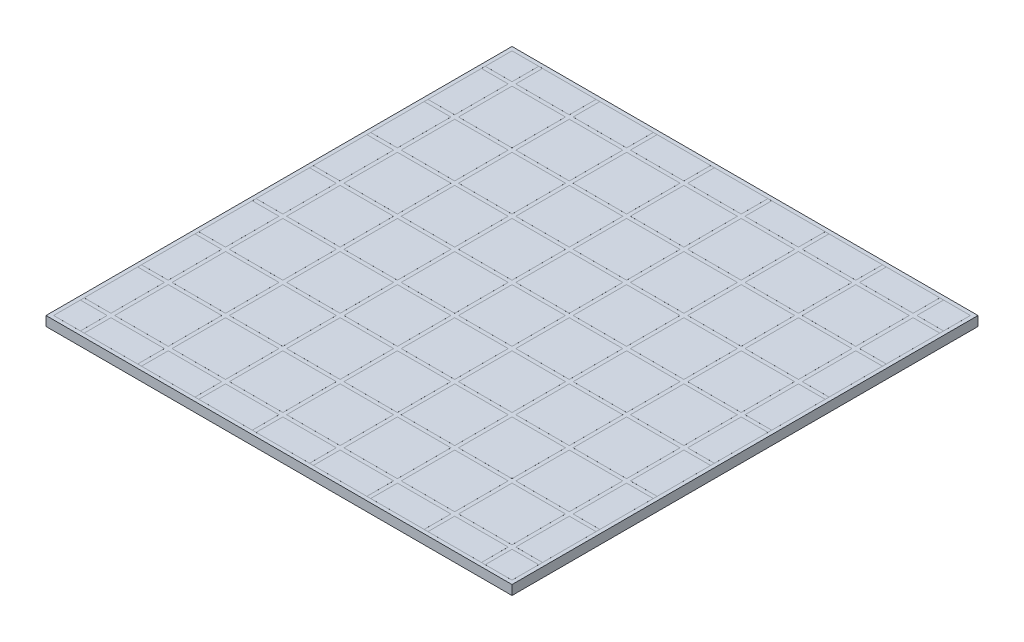
SolidWorks part; units mm, degrees
ref_plane "Спереди" through (0, 0, 0) normal (0, 0, 1) x (1, 0, 0)
ref_plane "Сверху" through (0, 0, 0) normal (0, 1, 0) x (1, 0, 0)
ref_plane "Справа" through (0, 0, 0) normal (1, 0, 0) x (0, 0, -1)
sketch "Эскиз1" plane through (0, 0, 0) normal (0, 1, 0) x (1, 0, 0)
  line L1 (-1220, -1220) -> (1220, -1220)
  line L2 (-1220, -1220) -> (-1220, 1220)
  line L3 (-1220, 1220) -> (1220, 1220)
  line L4 (1220, -1220) -> (1220, 1220)
  line L5 (-1220, -1220) -> (1220, 1220) construction
  line L6 (-1220, 1220) -> (1220, -1220) construction
  point P0 (0, 0)
  dimension "D1" = 2440
extrude "Бобышка-Вытянуть1" add sketch "Эскиз1" against normal blind 50
sketch "Эскиз6" plane through (0, 0, 0) normal (0, 1, 0) x (1, 0, 0)
  line L0 (-1200, 1200) -> (-1200, -1200)
  line L1 (-1220, 1220) -> (1220, 1220)
  line L2 (-1220, 1220) -> (-1220, -1220)
  line L3 (-1220, -1220) -> (1220, -1220)
  line L4 (1220, 1220) -> (1220, -1220)
  line L5 (-1200, -1200) -> (1200, -1200)
  line L6 (1200, 1200) -> (1200, -1200)
  line L7 (-1200, 1200) -> (1200, 1200)
  line L8 (-1060, -1200) -> (-1060, 1200)
  line L9 (-1040, -1200) -> (-1040, 1200)
  line L10 (-760, -1200) -> (-760, 1200)
  line L11 (-740, -1200) -> (-740, 1200)
  line L12 (-460, -1200) -> (-460, 1200)
  line L13 (-440, -1200) -> (-440, 1200)
  line L14 (-160, -1200) -> (-160, 1200)
  line L15 (-140, -1200) -> (-140, 1200)
  line L16 (140, -1200) -> (140, 1200)
  line L17 (160, -1200) -> (160, 1200)
  line L18 (440, -1200) -> (440, 1200)
  line L19 (460, -1200) -> (460, 1200)
  line L20 (740, -1200) -> (740, 1200)
  line L21 (760, -1200) -> (760, 1200)
  line L22 (1040, -1200) -> (1040, 1200)
  line L23 (1060, -1200) -> (1060, 1200)
  line L24 (-1200, 1060) -> (1200, 1060)
  line L25 (-1200, 1040) -> (1200, 1040)
  dimension "D2" = 140
  dimension "D3" = 20
  dimension "D5" = 140
  dimension "D6" = 140
  dimension "D7" = 20
  dimension "D1" = 20
  dimension "D4" = 8
sketch "Эскиз8" plane through (0, 0, 0) normal (0, 1, 0) x (1, 0, 0)
  line L4 (1220, -1220) -> (1220, 1220)
  line L5 (1220, 1220) -> (-1220, 1220)
  line L6 (-1220, 1220) -> (-1220, -1220)
  line L7 (-1220, -1220) -> (1220, -1220)
  line L8 (1220, -1220) -> (1220, 1220)
  line L9 (1220, 1220) -> (-1220, 1220)
  line L10 (-1220, 1220) -> (-1220, -1220)
  line L11 (-1220, -1220) -> (1220, -1220)
  dimension "D1" = 0
extrude "Вырез-Вытянуть-Тонкостенный1" cut sketch "Эскиз8" against normal blind 0.1 thin thin type one direction reverse wall 20
sketch "Эскиз9" plane through (0, 0, 0) normal (0, 1, 0) x (1, 0, 0)
  line L0 (-1060, 1291.4931) -> (-1060, -1337.4537)
  line L1 (-1200, 1200) -> (-1200, -1200) construction
  dimension "D1" = 140
extrude "Вырез-Вытянуть-Тонкостенный2" cut sketch "Эскиз9" against normal up to surface (0.1 mm away) and the other way through all thin up to face at (0, -0.1, 0) thin type one direction reverse wall 20
pattern_linear "Линейный массив1" count 10 spacing 300 along (1, 0, 0) of "Вырез-Вытянуть-Тонкостенный2"
ref_axis "Ось1" through (0, -50, 0) along (0, 1, 0)
pattern_circular "Круговой массив1" count 2 every 90 about axis through (0, -50, 0) along (0, 1, 0) of "Линейный массив1"
sketch "Эскиз10" plane through (0, -0.1, 0) normal (0, 1, 0) x (1, 0, 0)
  line L1 (-1220, 1220) -> (1220, 1220)
  line L2 (-1220, 1220) -> (-1220, -1220)
  line L3 (-1220, -1220) -> (1220, -1220)
  line L4 (-1220, 1220) -> (-1220, -1220)
  line L5 (-1220, -1220) -> (1220, -1220)
  line L6 (1220, -1220) -> (1220, 1220)
  line L7 (1220, 1220) -> (-1220, 1220)
  line L8 (-1220, 1220) -> (-1220, -1220)
  line L9 (-1220, -1220) -> (1220, -1220)
  line L10 (1220, -1220) -> (1220, 1220)
  line L11 (1220, 1220) -> (-1220, 1220)
  line L12 (1220, 1220) -> (1220, -1220)
  line L13 (1200, -1200) -> (-1200, -1200)
  line L14 (1200, -1200) -> (1200, 1200)
  line L15 (1200, 1200) -> (-1200, 1200)
  line L16 (-1200, -1200) -> (-1200, 1200)
  dimension "D1" = 0
extrude "Бобышка-Вытянуть3" add sketch "Эскиз10" along normal blind 0.05 contours L3 L10 L1 L2 L13 L16 L15 L14 region at (0, -0.1, -1216.5493)
